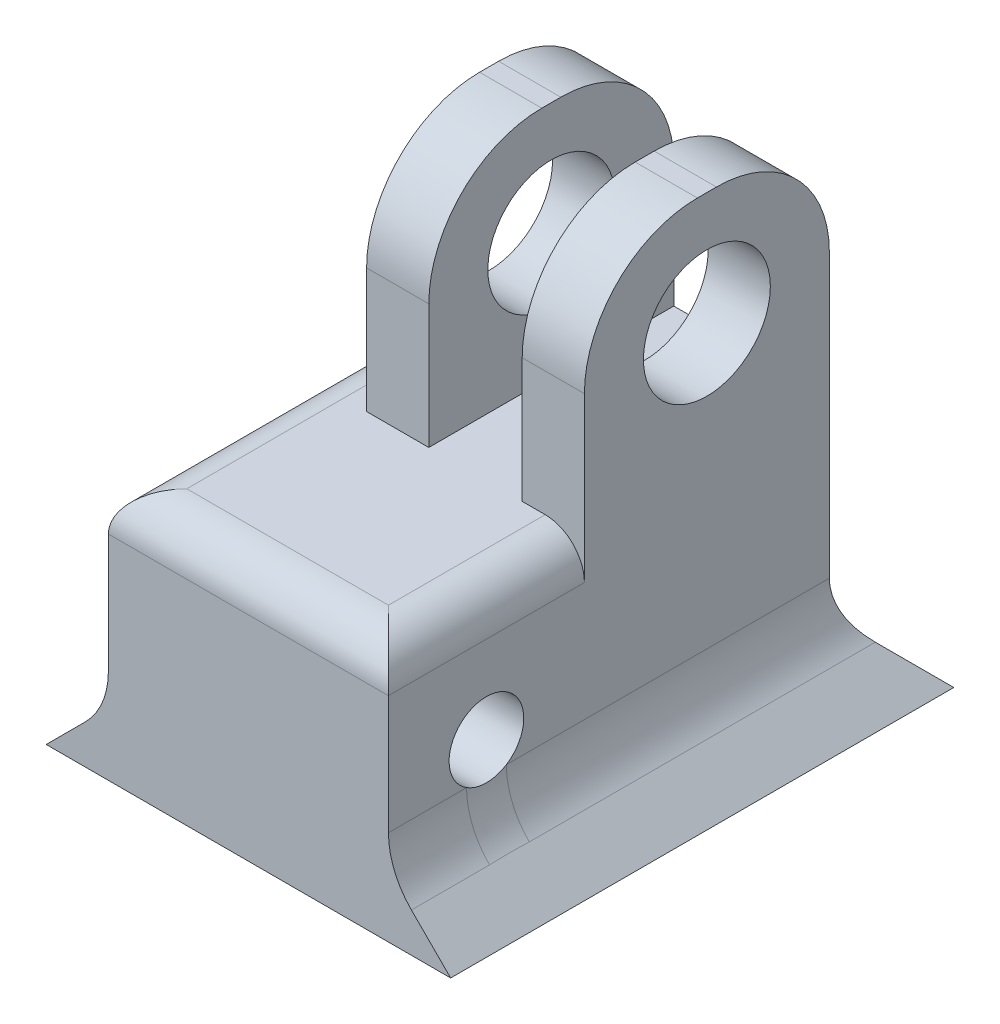
SolidWorks part; units mm, degrees
ref_plane "Front Plane" through (0, 0, 0) normal (0, 0, 1) x (1, 0, 0)
ref_plane "Top Plane" through (0, 0, 0) normal (0, 1, 0) x (1, 0, 0)
ref_plane "Right Plane" through (0, 0, 0) normal (1, 0, 0) x (0, 0, -1)
sketch "Sketch1" plane through (0, 0, 0) normal (0, 0, 1) x (1, 0, 0)
  line L1 (-14.29, -25) -> (14.29, -25)
  line L2 (-14.29, -25) -> (-14.29, 25)
  line L3 (-14.29, 25) -> (14.29, 25)
  line L4 (14.29, -25) -> (14.29, 25)
  line L5 (-14.29, -25) -> (14.29, 25) construction
  line L6 (-14.29, 25) -> (14.29, -25) construction
  point P0 (0, 0)
  dimension "D1" = 50
  dimension "D2" = 28.58
extrude "Boss-Extrude1" add sketch "Sketch1" along normal mid plane 25
sketch "Sketch2" plane through (0, 0, 12.5) normal (0, 0, 1) x (-1, 0, 0)
  line L1 (-7.94, -0.775) -> (1.59, -0.775)
  line L2 (-7.94, -0.775) -> (-7.94, -25)
  line L3 (-7.94, -25) -> (1.59, -25)
  line L4 (1.59, -0.775) -> (1.59, -25)
  line L5 (7.94, -0.775) -> (14.29, -0.775)
  line L6 (7.94, -0.775) -> (7.94, -25)
  line L7 (7.94, -25) -> (14.29, -25)
  line L8 (14.29, -0.775) -> (14.29, -25)
  line L10 (-14.29, -25) -> (14.29, -25) construction
  line L11 (14.29, -25) -> (14.29, 25) construction
  line L12 (-14.29, 25) -> (-14.29, -25) construction
  dimension "D1" = 6.35
  dimension "D2" = 6.35
  dimension "D3" = 24.225
  dimension "D4" = 6.35
extrude "Cut-Extrude1" cut sketch "Sketch2" against normal through all
fillet "Fillet1" radius 11.53 4 edges at (-4.765, 25, -12.5) (-4.765, 25, 12.5) (11.115, 25, 12.5) (11.115, 25, -12.5)
sketch "Sketch3" plane through (14.29, 0, 0) normal (1, 0, 0) x (0, 0, -1)
  line L0 (-11.4063, 13.47) -> (20.1617, 13.47) construction
  line L1 (0, 37.5) -> (0, -49962.5) construction
  line L2 (-0.97, 25) -> (0.97, 25) construction
  circle A0 centre (0, 13.47) radius 6.477
  point P9 (0, 25)
  dimension "D1" = 12.954
extrude "Cut-Extrude2" cut sketch "Sketch3" against normal through all
sketch "Sketch4" plane through (14.29, 0, 0) normal (1, 0, 0) x (0, 0, -1)
  line L0 (-15.659, -25) -> (49984.341, -25) construction
  line L2 (-12.5, -25) -> (12.5, -25) construction
  line L3 (18.85, -25) -> (12.5, -18.65)
  line L4 (12.5, -25) -> (12.5, 13.47) construction
  line L5 (12.5, -18.65) -> (12.5, -25)
  line L6 (12.5, -25) -> (18.85, -25)
  dimension "D1" = 6.35
  dimension "D2" = 45
extrude "Boss-Extrude2" add sketch "Sketch4" against normal up to surface (28.58 mm away) up to face at (-14.29, -12.1125, 0)
sketch "Sketch5" plane through (0, 0, 12.5) normal (0, 0, 1) x (1, 0, 0)
  line L0 (-1.59, 0.775) -> (7.94, 0.775) construction
  line L1 (-14.29, -25) -> (14.29, -25)
  line L2 (-14.29, -25) -> (-14.29, 0.775)
  line L3 (-14.29, 0.775) -> (14.29, 0.775)
  line L4 (14.29, -25) -> (14.29, 0.775)
  line L5 (14.29, -25) -> (14.29, 13.47) construction
extrude "Boss-Extrude3" add sketch "Sketch5" along normal blind 20
sketch "Sketch6" plane through (14.29, 0, 0) normal (1, 0, 0) x (0, 0, -1)
  line L0 (-22.5, 0.775) -> (-22.5, -27.4392) construction
  line L2 (-29.7474, -12.1125) -> (-35.2025, -12.1125) construction
  line L4 (-32.5, 0.775) -> (-12.5, 0.775) construction
  circle A0 centre (-22.5, -12.1125) radius 3.81
  point P4 (-24.1987, -12.1125)
  point P5 (0, 0)
  point P10 (-22.5, 0.775)
  dimension "D1" = 7.62
extrude "Cut-Extrude3" cut sketch "Sketch6" against normal through all both and the other way through all
sketch "Sketch7" plane through (0, 0, -12.5) normal (0, 0, -1) x (-1, 0, 0)
  line L0 (-14.29, -25) -> (-20.64, -25)
  line L1 (-20.64, -25) -> (-14.29, -18.65)
  line L2 (-14.29, -18.65) -> (-14.29, 13.47) construction
  line L3 (14.29, -25) -> (-14.29, -25) construction
  line L4 (-14.29, -25) -> (-14.29, -18.65) construction
  line L5 (-14.29, -18.65) -> (-14.29, -25)
  dimension "D1" = 45
  dimension "D2" = 6.35
extrude "Boss-Extrude4" add sketch "Sketch7" against normal up to surface and the other way up to surface up to face at (0, -12.1125, 32.5) other way up to face at (0, -21.825, -15.675)
mirror "Mirror2" about plane through (0, 0, 0) normal (1, 0, 0) of "Boss-Extrude4"
hole_wizard "Ø5.0mm Dowel Hole1" positions "Sketch9" profile "Sketch11" hole size "Ø5.0" standard "ANSI Metric"
sketch "Sketch9" plane through (0, -25, 0) normal (0, -1, 0) x (-1, 0, 0)
  point P0 (-7.5, 0.5343)
  point P3 (7.5, 0.5343)
  point P6 (7.5, -14.4657)
  point P9 (-7.5, -14.4657)
sketch "Sketch11" plane through (7.5, -25, -0.5343) normal (1, 0, 0) x (0, 0, -1)
  line L0 (0, 0) -> (0, 11.5022)
  line L1 (0, 11.5022) -> (2.5, 10)
  line L2 (2.5, 10) -> (2.5, 0)
  line L5 (2.5, 0) -> (0, 0)
  line L10 (0, 11.5022) -> (-2.5, 10) construction
  line L11 (0, -6.35) -> (0, 107.95) construction
  dimension "Hole Dia." = 5
  dimension "Hole Depth" = 10
  dimension "Drill Angle" = 118
fillet "Fillet2" radius 8 3 edges at (-14.29, -18.65, 10) (14.29, -18.65, 10) (0, -18.65, -12.5)
fillet "Fillet4" radius 4 3 edges at (14.29, 0.775, 22.5) (0, 0.775, 32.5) (-14.29, 0.775, 10)
